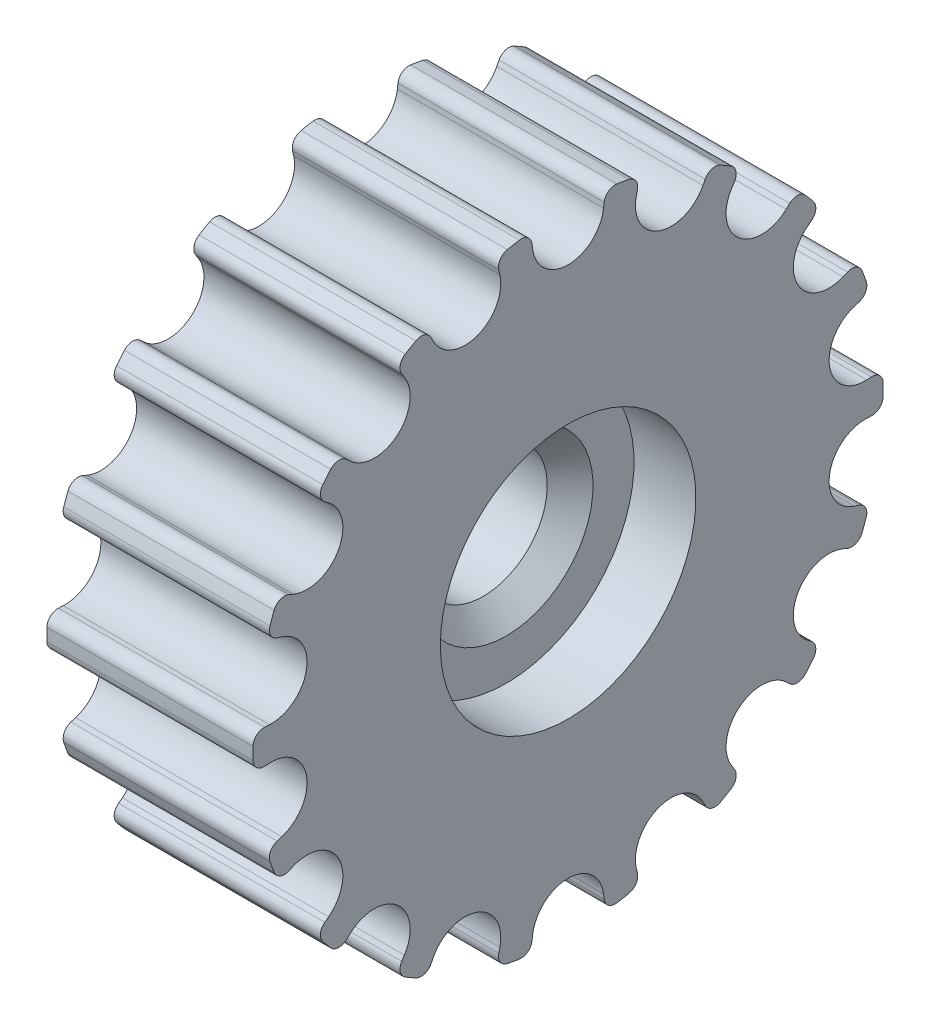
SolidWorks part; units mm, degrees
ref_plane "前视基准面" through (0, 0, 0) normal (0, 0, 1) x (1, 0, 0)
ref_plane "上视基准面" through (0, 0, 0) normal (0, 1, 0) x (1, 0, 0)
ref_plane "右视基准面" through (0, 0, 0) normal (1, 0, 0) x (0, 0, -1)
sketch "草图1" plane through (0, 0, 0) normal (0, 0, 1) x (1, 0, 0)
  line L0 (0, 0) -> (64.8368, 0) construction
  line L1 (0, 2.7888) -> (0, 13.753)
  line L2 (0, 13.753) -> (9, 13.753)
  line L3 (9, 13.753) -> (9, 5.5776)
  line L4 (9, 5.5776) -> (6.3, 5.5776)
  line L5 (6.3, 5.5776) -> (6.3, 2.7888)
  line L6 (6.3, 2.7888) -> (0, 2.7888)
  dimension "L" = 6.3
  dimension "B" = 9
  dimension "d" = 5.5776
  dimension "d1" = 11.1552
  dimension "da" = 27.506
revolve "旋转1" add sketch "草图1" angle 360 about L0
chamfer "倒角1" distance 1 angle 45 2 edges at (6.3, 0, 2.7888) (0, 0, 2.7888)
sketch "草图4" plane through (0, 0, 0) normal (-1, 0, 0) x (0, 0, 1)
  line L1 (-1, 2.6033) -> (1, 2.6033)
  line L2 (-1, 2.6033) -> (-1, 3.7888)
  line L3 (-1, 3.7888) -> (1, 3.7888)
  line L4 (1, 2.6033) -> (1, 3.7888)
  circle A0 centre (0, 0) radius 2.7888 construction
  point P6 (0, 3.7888)
  dimension "键槽高度" = 3.7888
  dimension "键槽宽度" = 2
  dimension "t1" = 1
extrude "切除-拉伸1" cut sketch "草图4" against normal through all
sketch "草图6" plane through (0, 0, 0) normal (1, 0, 0) x (0, 0, -1)
  line L0 (0, 0) -> (0, 30.6512) construction
  line L1 (1.5741, 13.1722) -> (1.5484, 12.9629)
  line L2 (2.5975, 13.5055) -> (2.7942, 15.107)
  line L3 (-2.5975, 13.5055) -> (-2.7942, 15.107)
  line L4 (-1.5741, 13.1722) -> (-1.5484, 12.9629)
  circle A0 centre (0, 0) radius 13.753 construction
  circle A1 centre (0, 0) radius 11.593 construction
  arc A2 (-1.5484, 12.9629) -> (1.5484, 12.9629) centre (0, 13.153) ccw
  arc A3 (2.7942, 15.107) -> (-2.7942, 15.107) centre (0, 0) ccw
  arc A4 (1.5741, 13.1722) -> (2.1246, 13.5879) centre (2.0505, 13.1137) cw
  arc A5 (2.1246, 13.5879) -> (2.5975, 13.5055) centre (0, 0) cw
  arc A6 (-2.1246, 13.5879) -> (-2.5975, 13.5055) centre (0, 0) ccw
  arc A7 (-1.5741, 13.1722) -> (-2.1246, 13.5879) centre (-2.0505, 13.1137) ccw
  point P7 (0, 3.25)
  point P8 (0, 28.4912)
  point P15 (1.6334, 13.6557)
  dimension "D1" = 23.186
  dimension "ra" = 0.48
  dimension "rf" = 1.56
  dimension "hg" = 2.16
  dimension "D3" = 0.48
  dimension "D4" = 1.6136
  dimension "angle" = 14
  dimension "bw" = 3.25
extrude "切除-拉伸2" cut sketch "草图6" along normal up to next
ref_axis "基准轴1" through (-1.4, 0, 0) along (1, 0, 0)
pattern_circular "阵列(圆周)3" count 18 over 360 about axis through (-1.4, 0, 0) along (1, 0, 0) of "切除-拉伸2"
equation "\"键槽高度@草图4\" = \"d@草图1\" / 2  + \"t1@草图4\""
equation "\"D1@草图6\" = \"da@草图1\"  - \"hg@草图6\" - \"hg@草图6\""
equation "\"D3@草图6\" = \"ra@草图6\""
